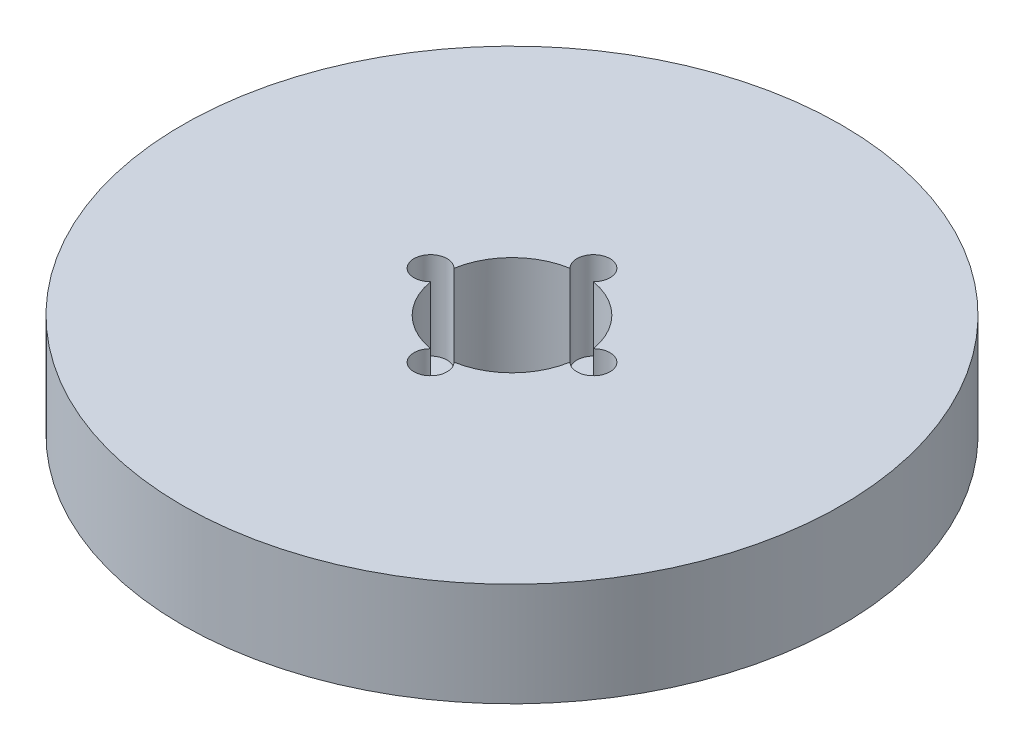
SolidWorks part; units mm, degrees
ref_plane "Front Plane" through (0, 0, 0) normal (0, 0, 1) x (1, 0, 0)
ref_plane "Top Plane" through (0, 0, 0) normal (0, 1, 0) x (1, 0, 0)
ref_plane "Right Plane" through (0, 0, 0) normal (1, 0, 0) x (0, 0, -1)
sketch "Sketch1" plane through (0, 0, 0) normal (0, 1, 0) x (1, 0, 0)
  circle A0 centre (0, 0) radius 35
  dimension "FLANGE_OD" = 70
extrude "Boss-Extrude1" add sketch "Sketch1" along normal blind 11
sketch "Sketch2" plane through (0, 0, 0) normal (0, 1, 0) x (1, 0, 0)
  circle A0 centre (0, 0) radius 7.5
  dimension "BORE_D" = 15
extrude "Cut-Extrude1" cut sketch "Sketch2" along normal through all
sketch "Sketch3" plane through (0, 11, 0) normal (0, 1, 0) x (1, 0, 0)
  circle A0 centre (0, 0) radius 8.6512 construction
  circle A1 centre (-8.6512, 0) radius 1.7601
  dimension "BOLT_D" = 3.5202
  dimension "BOLT_PCD" = 17.3023
extrude "Cut-Extrude2" cut sketch "Sketch3" against normal blind 9.331
pattern_circular "CirPattern1" count 4 over 360 about axis through (0, 0, 0) along (0, 1, 0) of "Cut-Extrude2"
